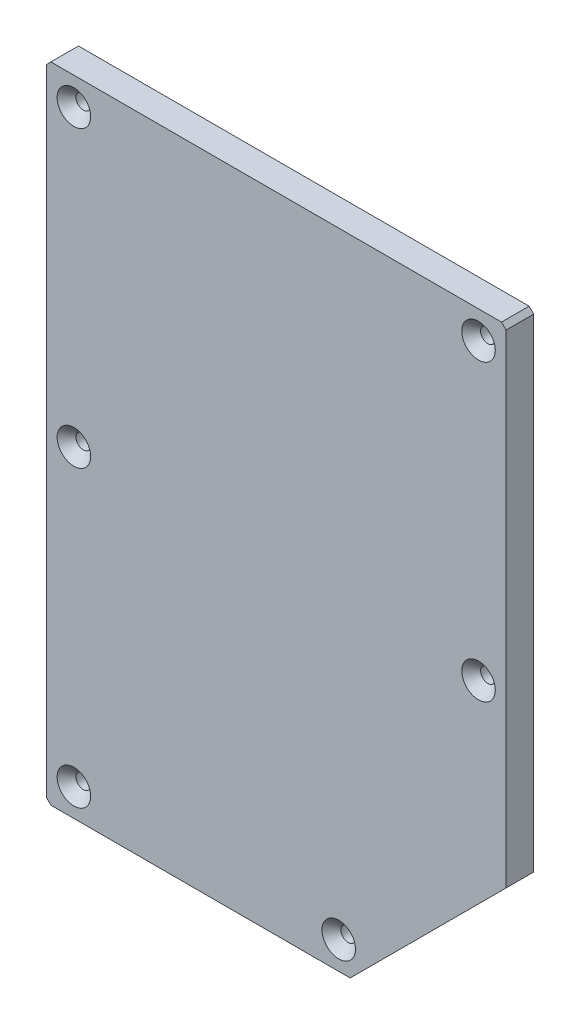
SolidWorks part; units mm, degrees
ref_plane "Front Plane" through (0, 0, 0) normal (0, 0, 1) x (1, 0, 0)
ref_plane "Top Plane" through (0, 0, 0) normal (0, 1, 0) x (1, 0, 0)
ref_plane "Right Plane" through (0, 0, 0) normal (1, 0, 0) x (0, 0, -1)
sketch "Sketch1" plane through (0, 0, 0) normal (0, 0, 1) x (1, 0, 0)
  line L16 (60, -62.4854) -> (60, 42.5997)
  line L17 (60, 42.5997) -> (59, 43.5997)
  line L18 (59, 43.5997) -> (-39, 43.5997)
  line L19 (-39, 43.5997) -> (-40, 42.5997)
  line L20 (-40, 42.5997) -> (-40, -95.4003)
  line L21 (-40, -95.4003) -> (-39, -96.4003)
  line L22 (-39, -96.4003) -> (26.0851, -96.4003)
  line L23 (26.0851, -96.4003) -> (60, -62.4854)
  line L56 (60, -62.4854) -> (60, 42.5997)
  line L57 (60, 42.5997) -> (59, 43.5997)
  line L58 (59, 43.5997) -> (-39, 43.5997)
  line L59 (-39, 43.5997) -> (-40, 42.5997)
  line L60 (-40, 42.5997) -> (-40, -95.4003)
  line L61 (-40, -95.4003) -> (-39, -96.4003)
  line L62 (-39, -96.4003) -> (26.0851, -96.4003)
  line L63 (26.0851, -96.4003) -> (60, -62.4854)
  dimension "D1" = 0
extrude "Boss-Extrude1" add sketch "Sketch1" along normal blind 6
hole_wizard "CSK for M3 Countersunk Flat Head Screw1" positions "3DSketch1" profile "Sketch4" countersink size "M3" standard "ISO" end condition up to next
sketch3d "3DSketch1"
  point P0 (-34, 37.5997, 6)
  point P2 (54, 37.5997, 6)
  point P4 (54, -26.4003, 6)
  point P18 (23.5999, -90.4003, 6)
  point P20 (-34, -90.4003, 6)
  point P22 (-34, -26.4003, 6)
sketch "Sketch4" plane through (-34, 37.5997, 6) normal (1, 0, 0) x (0, -1, 0)
  line L0 (0, 0) -> (0, 6)
  line L1 (0, 6) -> (1.6, 6)
  line L2 (1.6, 6) -> (1.6, 2.05)
  line L3 (1.6, 2.05) -> (3.65, 0)
  line L5 (3.65, 0) -> (0, 0)
  line L6 (-1.6, 2.05) -> (-3.65, 0) construction
  line L11 (0, -6.35) -> (0, 107.95) construction
  dimension "Thru Hole Dia." = 3.2
  dimension "Thru Hole Depth" = 6
  dimension "Near C'Sink Dia." = 7.3
  dimension "Near C'Sink Angle" = 90
